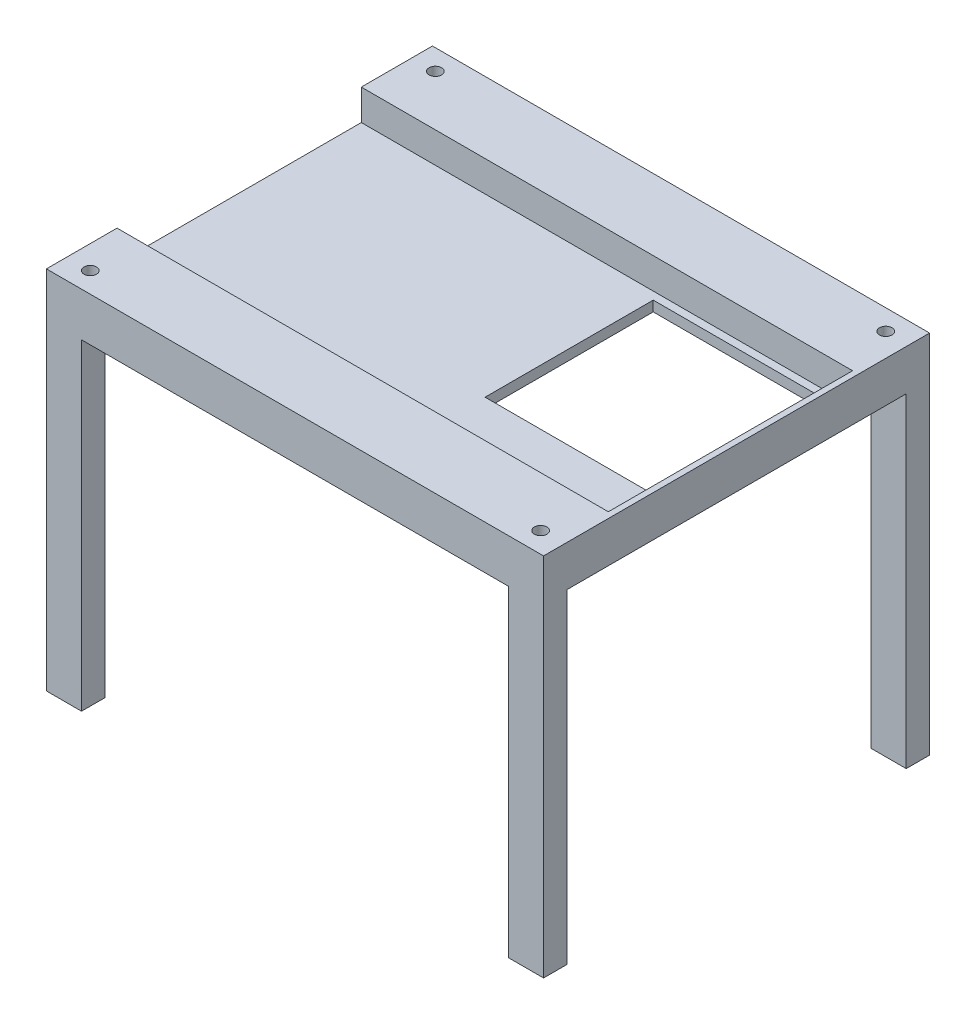
SolidWorks part; units mm, degrees
ref_plane "Front Plane" through (0, 0, 0) normal (0, 0, 1) x (1, 0, 0)
ref_plane "Top Plane" through (0, 0, 0) normal (0, 1, 0) x (1, 0, 0)
ref_plane "Right Plane" through (0, 0, 0) normal (1, 0, 0) x (0, 0, -1)
sketch "Sketch1" plane through (0, 0, 0) normal (0, 1, 0) x (1, 0, 0)
  line L1 (0, 0) -> (165, 0)
  line L2 (0, 0) -> (0, 82)
  line L3 (0, 82) -> (165, 82)
  line L4 (165, 0) -> (165, 82)
  line L5 (100, 2) -> (163, 2)
  line L6 (100, 2) -> (100, 80)
  line L7 (100, 80) -> (163, 80)
  line L8 (163, 2) -> (163, 80)
  line L9 (-2.5, -2.5) -> (167.5, -2.5)
  line L10 (-2.5, -2.5) -> (-2.5, 84.5)
  line L11 (-2.5, 84.5) -> (167.5, 84.5)
  line L12 (167.5, -2.5) -> (167.5, 84.5)
  dimension "D1" = 165
  dimension "D2" = 82
  dimension "D3" = 2
  dimension "D4" = 2
  dimension "D5" = 2
  dimension "D6" = 65
  dimension "D7" = 2.5
  dimension "D8" = 2.5
  dimension "D9" = 2.5
  dimension "D10" = 170
extrude "Boss-Extrude5" add sketch "Sketch1<9>" along normal blind 2 separate body contours L9 L12 L11 L10
sketch "Sketch1<9>" plane through (0, 0, 0) normal (0, 1, 0) x (1, 0, 0) same geometry as "Sketch1"
extrude "Cut-Extrude3" cut sketch "Sketch1<10>" along normal blind 9 contours L6 L7 L8 L5
sketch "Sketch1<10>" plane through (0, 0, 0) normal (0, 1, 0) x (1, 0, 0) same geometry as "Sketch1"
extrude "Boss-Extrude6" add sketch "Sketch1<12>" along normal blind 14 contours L11 L12 L9 L10
sketch "Sketch1<12>" plane through (0, 0, 0) normal (0, 1, 0) x (1, 0, 0) same geometry as "Sketch1"
extrude "Cut-Extrude4" cut sketch "Sketch1" along normal blind 29 contours L7 L8 L5 L6
sketch "Sketch8" plane through (-2.5, 0, 0) normal (-1, 0, 0) x (0, 0, 1)
  line L0 (2.5, 14) -> (-84.5, 14) construction
  line L1 (-82.6737, 14) -> (0.8523, 14)
  line L2 (-82.6737, 14) -> (-82.6737, 3.5)
  line L3 (-82.6737, 3.5) -> (0.8523, 3.5)
  line L4 (0.8523, 14) -> (0.8523, 3.5)
  line L5 (2.5, 0) -> (-84.5, 0) construction
  dimension "D1" = 0
  dimension "D2" = 3.5
extrude "Cut-Extrude5" cut sketch "Sketch8" against normal blind 168 contours L3 L4 L1 L2
sketch "Sketch11" plane through (0, 0, 2.5) normal (0, 0, 1) x (1, 0, 0)
  line L1 (-2.5, 14) -> (90, 14)
  line L3 (-2.5, 9) -> (90, 9)
  line L5 (90, 14) -> (167.5, 14)
  line L6 (167.5, 14) -> (167.5, 9)
  line L7 (167.5, 14) -> (167.5, 0) construction
  line L8 (167.5, 9) -> (90, 9)
  line L9 (-2.5, 14) -> (-2.5, 9)
  dimension "D4" = 5
extrude "Boss-Extrude10" add sketch "Sketch11" along normal blind 22.5 contours L3 L8 L6 L5 L1 L9
ref_plane "Plane11" through (0, 0, -41) normal (0, 0, 1) x (1, 0, 0)
mirror "Mirror10" about plane through (0, 0, -41) normal (0, 0, 1) of "Boss-Extrude10"
sketch "Sketch45" plane through (0, 0, 2.5) normal (0, 0, 1) x (1, 0, 0)
  line L1 (-2.5, 9) -> (167.5, 9)
  line L2 (-2.5, 9) -> (-2.5, 0)
  line L3 (-2.5, 0) -> (167.5, 0)
  line L4 (167.5, 9) -> (167.5, 0)
chamfer "Chamfer1" distance 10 angle 45 1 edges at (82.5, 9, 2.5)
chamfer "Chamfer2" distance 10 angle 45 1 edges at (82.5, 9, -84.5)
sketch "Sketch47" plane through (0, 14, 0) normal (0, 1, 0) x (1, 0, 0)
  line L0 (-2.5, 107) -> (167.5, 107) construction
  line L1 (167.5, -25) -> (167.5, 107) construction
  line L2 (-2.5, 82.6737) -> (-2.5, 107) construction
  line L3 (-55, 41) -> (55, 41) construction
  circle A0 centre (5.5, 100) radius 2.15
  circle A1 centre (159.5, 100) radius 2.15
  circle A2 centre (159.5, -18) radius 2.15
  circle A3 centre (5.5, -18) radius 2.15
  dimension "D1" = 4.3
  dimension "D2" = 7
  dimension "D3" = 4.3
  dimension "D4" = 7
  dimension "D5" = 8
  dimension "D6" = 8
extrude "Cut-Extrude10" cut sketch "Sketch47" against normal blind 9.5
sketch "Sketch37" plane through (0, 0, 2.5) normal (0, 0, 1) x (1, 0, 0)
  line L0 (167.5, 9) -> (167.5, 0) construction
  line L1 (-2.5, 9) -> (167.5, 9)
  line L2 (-2.5, 9) -> (-2.5, 0)
  line L3 (-2.5, 0) -> (167.5, 0)
  line L4 (167.5, 9) -> (167.5, 0)
  line L5 (-2.5, 0) -> (167.5, 0) construction
extrude "Boss-Extrude20" add sketch "Sketch37" along normal blind 5
sketch "Sketch25" plane through (0, 9, 0) normal (0, -1, 0) x (1, 0, 0)
  line L0 (167.5, -107) -> (167.5, -94.5) construction
  line L1 (-2.5, -107) -> (167.5, -107)
  line L2 (-2.5, -107) -> (-2.5, -99)
  line L3 (-2.5, -99) -> (167.5, -99)
  line L4 (167.5, -107) -> (167.5, -99)
  dimension "D1" = 8
extrude "Boss-Extrude18" add sketch "Sketch25" along normal blind 120 contours L3 L4 L1 L2
sketch "Sketch28" plane through (0, 9, 0) normal (0, -1, 0) x (1, 0, 0)
  line L0 (-2.5, 25) -> (167.5, 25) construction
  line L1 (-2.5, 25) -> (167.5, 25)
  line L2 (-2.5, 25) -> (-2.5, 17)
  line L3 (-2.5, 17) -> (167.5, 17)
  line L4 (167.5, 25) -> (167.5, 17)
  line L5 (167.5, 25) -> (167.5, 12.5) construction
  dimension "D1" = 8
extrude "Boss-Extrude19" add sketch "Sketch28" along normal blind 120
mirror "Mirror11" about plane through (0, 0, -41) normal (0, 0, 1) of "Boss-Extrude20"
sketch "Sketch43" plane through (0, 0, 25) normal (0, 0, 1) x (1, 0, 0)
  line L0 (167.5, -111) -> (-2.5, -111) construction
  line L1 (9.5, -1) -> (155.5, -1)
  line L2 (9.5, -1) -> (9.5, -111)
  line L3 (9.5, -111) -> (155.5, -111)
  line L4 (155.5, -1) -> (155.5, -111)
  line L5 (167.5, 14) -> (167.5, -111) construction
  line L6 (-2.5, 14) -> (-2.5, -111) construction
  dimension "D1" = 110
  dimension "D2" = 12
  dimension "D3" = 12
extrude "Cut-Extrude9" cut sketch "Sketch43" against normal blind 170.5
sketch "Sketch38" plane through (0, 0, 7.5) normal (0, 0, 1) x (1, 0, 0)
  line L1 (-2.5, 9) -> (2.5, 9)
  line L2 (-2.5, 9) -> (-2.5, 0)
  line L3 (-2.5, 0) -> (2.5, 0)
  line L4 (2.5, 9) -> (2.5, 0)
  dimension "D1" = 5
sketch "Sketch42" plane through (0, 0, -2) normal (0, 0, -1) x (-1, 0, 0)
  line L0 (-100, 0) -> (-163, 0) construction
  line L1 (-163, 3.5) -> (-100, 3.5)
  line L2 (-163, 3.5) -> (-163, 0)
  line L3 (-163, 0) -> (-100, 0)
  line L4 (-100, 3.5) -> (-100, 0)
extrude "Boss-Extrude22" add sketch "Sketch42" along normal blind 20.5
extrude "Boss-Extrude23" add sketch "Sketch38" along normal blind 9.5
ref_plane "Plane4" through (82.5, 0, 0) normal (-1, 0, 0) x (0, 0, 1)
mirror "Mirror14" about plane through (0, 0, -41) normal (0, 0, 1) of "Boss-Extrude23" second plane through (82.5, 0, 0) second plane normal (-1, 0, 0)
